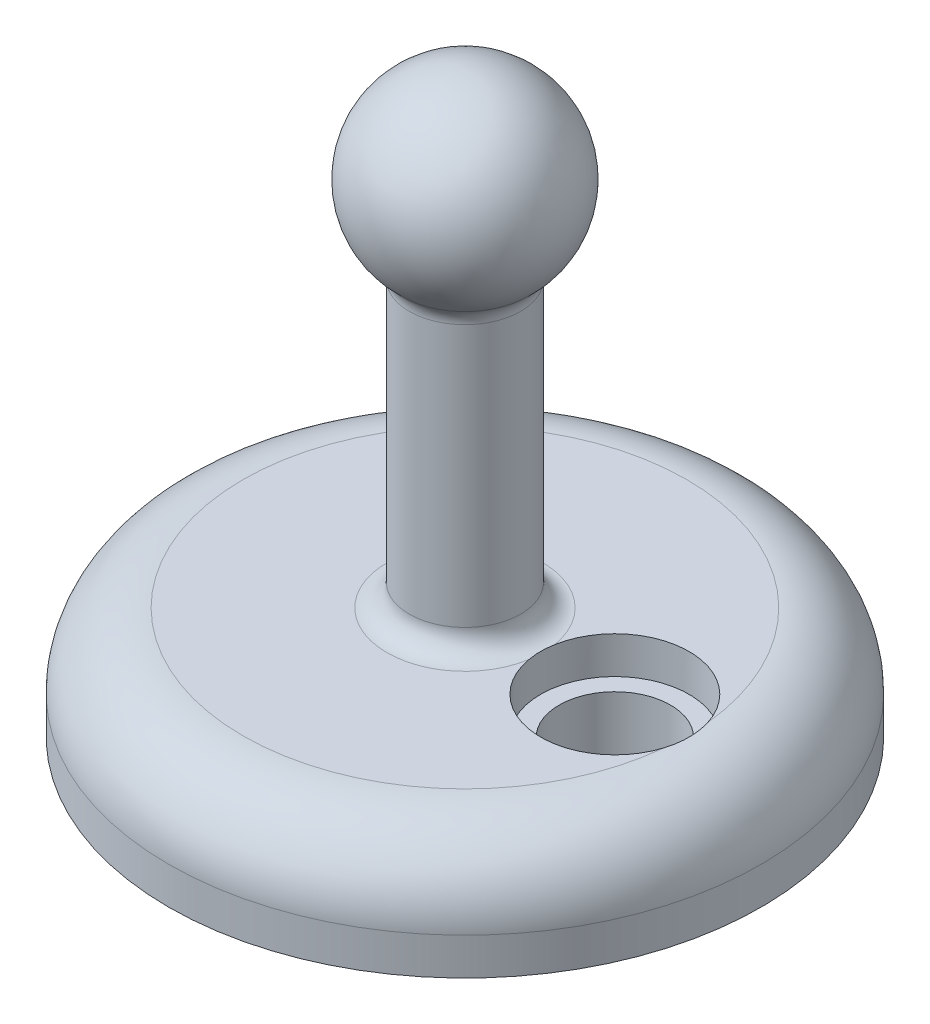
SolidWorks part; units mm, degrees
ref_plane "Front Plane" through (0, 0, 0) normal (0, 0, 1) x (1, 0, 0)
ref_plane "Top Plane" through (0, 0, 0) normal (0, 1, 0) x (1, 0, 0)
ref_plane "Right Plane" through (0, 0, 0) normal (1, 0, 0) x (0, 0, -1)
sketch "Sketch1" plane through (0, 0, 0) normal (0, 1, 0) x (1, 0, 0)
  line L0 (0, 34.9011) -> (0, 39.9011) construction
  circle A0 centre (0, 0) radius 39.9011
  circle A1 centre (0, 0) radius 34.9011 construction
  circle A2 centre (17.5, 28.3909) radius 1.55 construction
  dimension "D1" = 5
extrude "Boss-Extrude1" add sketch "Sketch1" along normal blind 15
fillet "Fillet1" radius 10 1 edges at (0, 15, 39.9011)
sketch "Sketch2" plane through (0, 0, 0) normal (0, -1, 0) x (1, 0, 0)
  circle A0 centre (-16.5, 28.5788) radius 1.55
  circle A1 centre (16.5, 28.5788) radius 1.55
  circle A2 centre (33, 0) radius 1.55
  circle A3 centre (16.5, -28.5788) radius 1.55
  circle A4 centre (-16.5, -28.5788) radius 1.55
  circle A5 centre (-33, 0) radius 1.55
  circle A6 centre (-35, 1.92) radius 1.55 construction
  circle A7 centre (-17.5, 32.2309) radius 1.55 construction
  circle A8 centre (17.5, 32.2309) radius 1.55 construction
  circle A9 centre (35, 1.92) radius 1.55 construction
  circle A10 centre (17.5, -28.3909) radius 1.55 construction
  circle A11 centre (-17.5, -28.3909) radius 1.55 construction
  circle A12 centre (-16.5, -28.5788) radius 1.55 construction
  circle A13 centre (-33, 0) radius 1.55 construction
  circle A14 centre (-16.5, 28.5788) radius 1.55 construction
  circle A16 centre (33, 0) radius 1.55 construction
  circle A17 centre (16.5, -28.5788) radius 1.55 construction
  circle A18 centre (16.5, 28.5788) radius 1.55 construction
extrude "Cut-Extrude1" cut sketch "Sketch2" against normal offset from surface (10 mm away) 5 up to face at (0, 15, 29.9011)
fillet "Fillet2" radius 1 6 edges at (33, 10, 1.55) (16.5, 10, -27.0288) (-16.5, 10, -27.0288) (-33, 10, 1.55) (-16.5, 10, 30.1288) (16.5, 10, 30.1288)
sketch "Sketch3" plane through (0, 0, 0) normal (0, -1, 0) x (1, 0, 0)
  circle A0 centre (-16.5, 28.5788) radius 2.5
  circle A1 centre (-33, 0) radius 2.5
  circle A2 centre (-16.5, -28.5788) radius 2.5
  circle A3 centre (16.5, -28.5788) radius 2.5
  circle A4 centre (33, 0) radius 2.5
  circle A5 centre (16.5, 28.5788) radius 2.5
  circle A6 centre (16.5, 28.5788) radius 1.55 construction
  circle A7 centre (-16.5, 28.5788) radius 1.55 construction
  circle A8 centre (-33, 0) radius 1.55 construction
  circle A9 centre (-16.5, -28.5788) radius 1.55 construction
  circle A10 centre (16.5, -28.5788) radius 1.55 construction
  circle A11 centre (33, 0) radius 1.55 construction
  dimension "D1" = 5
extrude "Cut-Extrude2" cut sketch "Sketch3" against normal blind 6
sketch "Sketch4" plane through (0, 15, 0) normal (0, 1, 0) x (1, 0, 0)
  circle A0 centre (0, 0) radius 7.5
  circle A1 centre (0, 0) radius 29.9011 construction
  dimension "D1" = 15
extrude "Boss-Extrude2" add sketch "Sketch4" along normal blind 50
sketch "Sketch5" plane through (0, 0, 0) normal (0, 0, 1) x (1, 0, 0)
  line L0 (7.5, 65) -> (-7.5, 65) construction
  line L1 (0, 77.7) -> (0, 52.3)
  circle A0 centre (0, 65) radius 12.7 construction
  arc A1 (0, 77.7) -> (0, 52.3) centre (0, 65) cw
  dimension "D1" = 25.4
revolve "Revolve1" add sketch "Sketch5" angle 360 about L1
fillet "Fillet3" radius 3 2 edges at (0, 54.7511, 7.5) (0, 15, 7.5)
sketch "Sketch6" plane through (0, 15, 0) normal (0, 1, 0) x (1, 0, 0)
  line L0 (29.9011, 0) -> (10.5, 0) construction
  circle A0 centre (20.2005, 0) radius 7.5
  circle A2 centre (0, 0) radius 29.9011 construction
  circle A3 centre (0, 0) radius 10.5 construction
  point P4 (20.2005, 0)
  dimension "D1" = 15
extrude "Cut-Extrude4" cut sketch "Sketch6" against normal up to surface (15 mm away) and the other way blind 10 up to face at (-33, 0, -2.5)
sketch "Sketch7" plane through (0, 15, 0) normal (0, 1, 0) x (1, 0, 0)
  circle A0 centre (20.2005, 0) radius 10
  circle A1 centre (20.2005, 0) radius 7.5 construction
  dimension "D1" = 20
extrude "Cut-Extrude5" cut sketch "Sketch7" against normal blind 5 and the other way blind 5
sketch "Sketch8" plane through (0, 0, 0) normal (0, -1, 0) x (1, 0, 0)
  line L0 (9.0494, 16.6616) -> (-32.4714, 16.6616) construction
  text T0 "^UP\r\nphonemonut V2\r\nhitchco-mk4"
extrude "Cut-Extrude6" cut sketch "Sketch8" against normal blind 1
